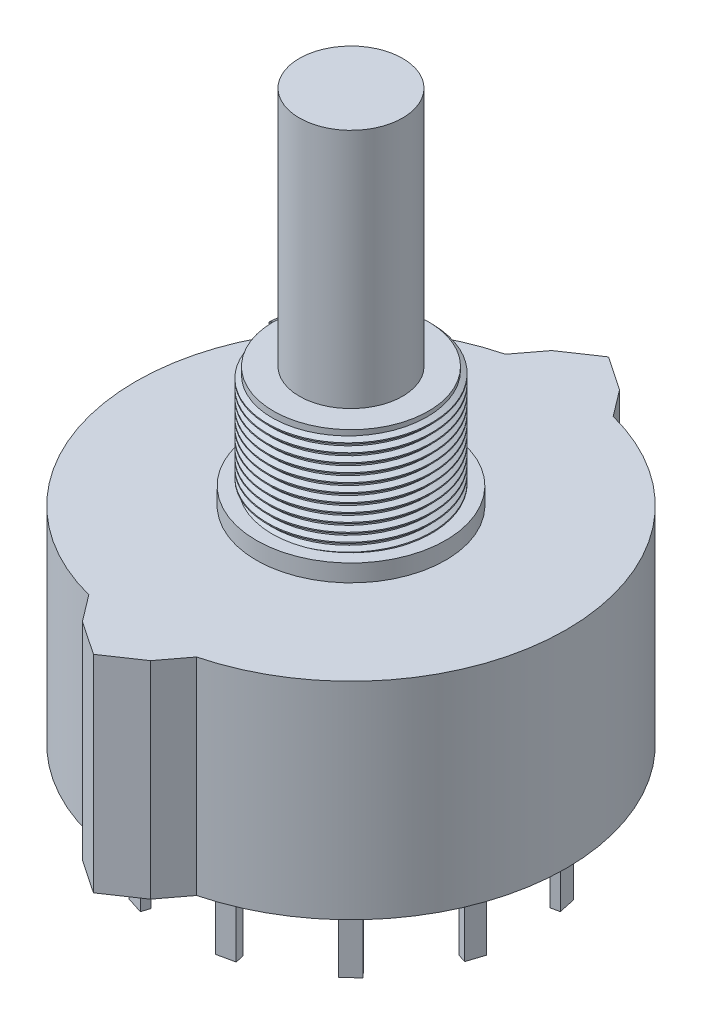
SolidWorks part; units mm, degrees
ref_plane "Спереди" through (0, 0, 0) normal (0, 0, 1) x (1, 0, 0)
ref_plane "Сверху" through (0, 0, 0) normal (0, 1, 0) x (1, 0, 0)
ref_plane "Справа" through (0, 0, 0) normal (1, 0, 0) x (0, 0, -1)
sketch "Эскиз1" plane through (0, 0, 0) normal (0, 1, 0) x (1, 0, 0)
  line L0 (-3.1279, 12.1023) -> (-1.9727, 13.6276)
  line L1 (-12.5, 0) -> (12.5, 0) construction
  line L2 (-1.9727, 13.6276) -> (0, 14.9612)
  line L3 (3.1279, -12.1023) -> (1.9727, -13.6276)
  line L4 (0, 14.9612) -> (0, 0) construction
  line L5 (1.9727, 13.6276) -> (0, 14.9612)
  line L6 (3.1279, 12.1023) -> (1.9727, 13.6276)
  line L7 (1.9727, -13.6276) -> (0, -14.9612)
  line L8 (-1.9727, -13.6276) -> (0, -14.9612)
  line L9 (-3.1279, -12.1023) -> (-1.9727, -13.6276)
  arc A0 (-3.1279, 12.1023) -> (-3.1279, -12.1023) centre (0, 0) ccw
  arc A1 (3.1279, -12.1023) -> (3.1279, 12.1023) centre (0, 0) ccw
  dimension "D1" = 25
extrude "Бобышка-Вытянуть1" add sketch "Эскиз1" along normal blind 12
sketch "Эскиз2" plane through (0, 12, 0) normal (0, 1, 0) x (1, 0, 0)
  circle A0 centre (0, 0) radius 5.5
extrude "Бобышка-Вытянуть2" add sketch "Эскиз2" along normal blind 1
sketch "Эскиз3" plane through (0, 13, 0) normal (0, 1, 0) x (1, 0, 0)
  circle A0 centre (0, 0) radius 4.5
extrude "Бобышка-Вытянуть3" add sketch "Эскиз3" along normal blind 6
sketch "Эскиз4" plane through (0, 19, 0) normal (0, 1, 0) x (1, 0, 0)
  circle A0 centre (0, 0) radius 3
extrude "Бобышка-Вытянуть4" add sketch "Эскиз4" along normal blind 14
sketch "Эскиз5" plane through (0, 0, 0) normal (0, -1, 0) x (1, 0, 0)
  line L0 (-12.5, 0) -> (12.5, 0) construction
  line L1 (-0.5, 5.75) -> (0.5, 5.75)
  line L2 (-0.5, 5.75) -> (-0.5, 5.25)
  line L3 (-0.5, 5.25) -> (0.5, 5.25)
  line L4 (0.5, 5.75) -> (0.5, 5.25)
  line L5 (-0.5, 5.75) -> (0.5, 5.25) construction
  line L6 (-0.5, 5.25) -> (0.5, 5.75) construction
  line L7 (-0.5, -5.25) -> (0.5, -5.75) construction
  line L8 (-0.5, -5.75) -> (0.5, -5.25) construction
  line L9 (0.5, -5.75) -> (0.5, -5.25)
  line L10 (-0.5, -5.25) -> (0.5, -5.25)
  line L11 (-0.5, -5.75) -> (-0.5, -5.25)
  line L12 (-0.5, -5.75) -> (0.5, -5.75)
  line L13 (0, 14.9612) -> (0, -14.9612) construction
  line L14 (0, -14.9612) -> (-1.9727, -13.6276) construction
  line L15 (0, 0) -> (8.8388, 8.8388) construction
  line L16 (6.868, 7.5919) -> (7.6096, 6.921)
  line L17 (6.868, 7.5919) -> (6.5326, 7.2211)
  line L18 (7.6096, 6.921) -> (7.2741, 6.5502)
  line L19 (7.2741, 6.5502) -> (6.5326, 7.2211)
  line L20 (9.7438, 3.1408) -> (10.0506, 2.189)
  line L21 (9.7438, 3.1408) -> (9.2679, 2.9874)
  line L22 (10.0506, 2.189) -> (9.5747, 2.0356)
  line L23 (9.5747, 2.0356) -> (9.2679, 2.9874)
  line L24 (10.0088, -2.1519) -> (9.7986, -3.1296)
  line L25 (10.0088, -2.1519) -> (9.5199, -2.0468)
  line L26 (9.7986, -3.1296) -> (9.3097, -3.0245)
  line L27 (9.3097, -3.0245) -> (9.5199, -2.0468)
  line L28 (7.5919, -6.868) -> (6.921, -7.6096)
  line L29 (7.5919, -6.868) -> (7.2211, -6.5326)
  line L30 (6.921, -7.6096) -> (6.5502, -7.2741)
  line L31 (6.5502, -7.2741) -> (7.2211, -6.5326)
  line L32 (3.1408, -9.7438) -> (2.189, -10.0506)
  line L33 (3.1408, -9.7438) -> (2.9874, -9.2679)
  line L34 (2.189, -10.0506) -> (2.0356, -9.5747)
  line L35 (2.0356, -9.5747) -> (2.9874, -9.2679)
  line L36 (-2.1519, -10.0088) -> (-3.1296, -9.7986)
  line L37 (-2.1519, -10.0088) -> (-2.0468, -9.5199)
  line L38 (-3.1296, -9.7986) -> (-3.0245, -9.3097)
  line L39 (-3.0245, -9.3097) -> (-2.0468, -9.5199)
  line L40 (-6.868, -7.5919) -> (-7.6096, -6.921)
  line L41 (-6.868, -7.5919) -> (-6.5326, -7.2211)
  line L42 (-7.6096, -6.921) -> (-7.2741, -6.5502)
  line L43 (-7.2741, -6.5502) -> (-6.5326, -7.2211)
  line L44 (-9.7438, -3.1408) -> (-10.0506, -2.189)
  line L45 (-9.7438, -3.1408) -> (-9.2679, -2.9874)
  line L46 (-10.0506, -2.189) -> (-9.5747, -2.0356)
  line L47 (-9.5747, -2.0356) -> (-9.2679, -2.9874)
  line L48 (-10.0088, 2.1519) -> (-9.7986, 3.1296)
  line L49 (-10.0088, 2.1519) -> (-9.5199, 2.0468)
  line L50 (-9.7986, 3.1296) -> (-9.3097, 3.0245)
  line L51 (-9.3097, 3.0245) -> (-9.5199, 2.0468)
  line L52 (-7.5919, 6.868) -> (-6.921, 7.6096)
  line L53 (-7.5919, 6.868) -> (-7.2211, 6.5326)
  line L54 (-6.921, 7.6096) -> (-6.5502, 7.2741)
  line L55 (-6.5502, 7.2741) -> (-7.2211, 6.5326)
  line L56 (-3.1408, 9.7438) -> (-2.189, 10.0506)
  line L57 (-3.1408, 9.7438) -> (-2.9874, 9.2679)
  line L58 (-2.189, 10.0506) -> (-2.0356, 9.5747)
  line L59 (-2.0356, 9.5747) -> (-2.9874, 9.2679)
  line L60 (2.1519, 10.0088) -> (3.1296, 9.7986)
  line L61 (2.1519, 10.0088) -> (2.0468, 9.5199)
  line L62 (3.1296, 9.7986) -> (3.0245, 9.3097)
  line L63 (3.0245, 9.3097) -> (2.0468, 9.5199)
  circle A0 centre (0, 0) radius 5.5 construction
  circle A1 centre (0, 0) radius 10 construction
  arc A2 (-3.1279, 12.1023) -> (-3.1279, -12.1023) centre (0, 0) ccw construction
  arc A3 (3.1279, -12.1023) -> (3.1279, 12.1023) centre (0, 0) ccw construction
  point P4 (0, 5.5)
  point P21 (0, -5.5)
  point P28 (7.0711, 7.0711)
  point P36 (9.6593, 2.5882)
  point P41 (9.6593, -2.5882)
  point P46 (7.0711, -7.0711)
  point P51 (2.5882, -9.6593)
  point P56 (-2.5882, -9.6593)
  point P61 (-7.0711, -7.0711)
  point P66 (-9.6593, -2.5882)
  point P71 (-9.6593, 2.5882)
  point P76 (-7.0711, 7.0711)
  point P81 (-2.5882, 9.6593)
  point P86 (2.5882, 9.6593)
  point P91 (0, 0)
  dimension "D1" = 1
  dimension "D5" = 0.25
  dimension "D6" = 0.5
  dimension "D2" = 0.5
  dimension "D3" = 1
  dimension "D4" = 0.5
  dimension "D7" = 12
extrude "Бобышка-Вытянуть5" add sketch "Эскиз5" along normal blind 4.5
thread "Резьба1" pitch 0.5 method extrude profile "Профиль резьбы2" start angle 0, offset 0, length 0, pitch 0.5, diameter 9
ref_plane "Плоскость5" through (-4.5, 19, 0) normal (0, 0, 1) x (-1, 0, 0)
sketch "Профиль резьбы2" plane through (-4.5, 19, 0) normal (0, 0, 1) x (-1, 0, 0)
  line L0 (0, 0) -> (0, 0.5) construction
  line L1 (0, 0) -> (0.2706, 0.1562)
  line L2 (0.2706, 0.1562) -> (0.2706, 0.2187)
  line L3 (0.2706, 0.2187) -> (0, 0.375)
  line L4 (0.2706, 0.1875) -> (0, 0.1875) construction
  line L11 (0, 0) -> (0, 0.375)
  point P2 (0, 0)
  dimension "Pitch" = 0.5
  dimension "Profile_Angle" = 60
  dimension "Profile_Land" = 0.0625
  dimension "Profile_Height" = 0.2706
